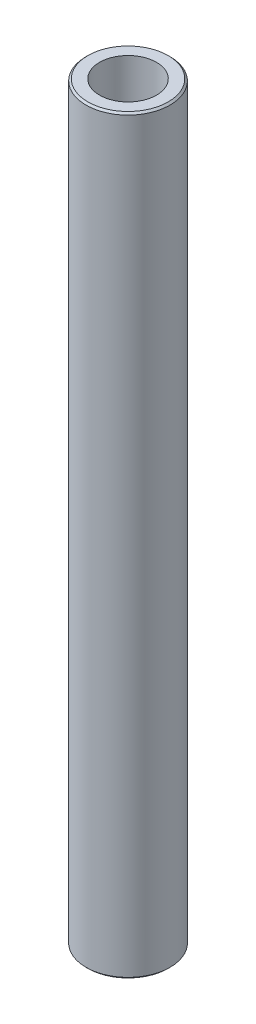
SolidWorks part; units mm, degrees
ref_plane "Front Plane" through (0, 0, 0) normal (0, 0, 1) x (1, 0, 0)
ref_plane "Top Plane" through (0, 0, 0) normal (0, 1, 0) x (1, 0, 0)
ref_plane "Right Plane" through (0, 0, 0) normal (1, 0, 0) x (0, 0, -1)
sketch "Sketch1" plane through (0, 0, 0) normal (0, 1, 0) x (1, 0, 0)
  circle A0 centre (0, 0) radius 12.5
  dimension "SHAFT_OD" = 25
extrude "Boss-Extrude1" add sketch "Sketch1" along normal blind 223.3759
sketch "Sketch2" plane through (0, 0, 0) normal (0, 1, 0) x (1, 0, 0)
  circle A0 centre (0, 0) radius 8.4788
  dimension "BORE_D" = 16.9576
extrude "Cut-Extrude1" cut sketch "Sketch2" along normal through all
chamfer "Chamfer1" distance 0.5462 angle 45 2 edges at (0, 223.3759, 12.5) (0, 0, 12.5)
